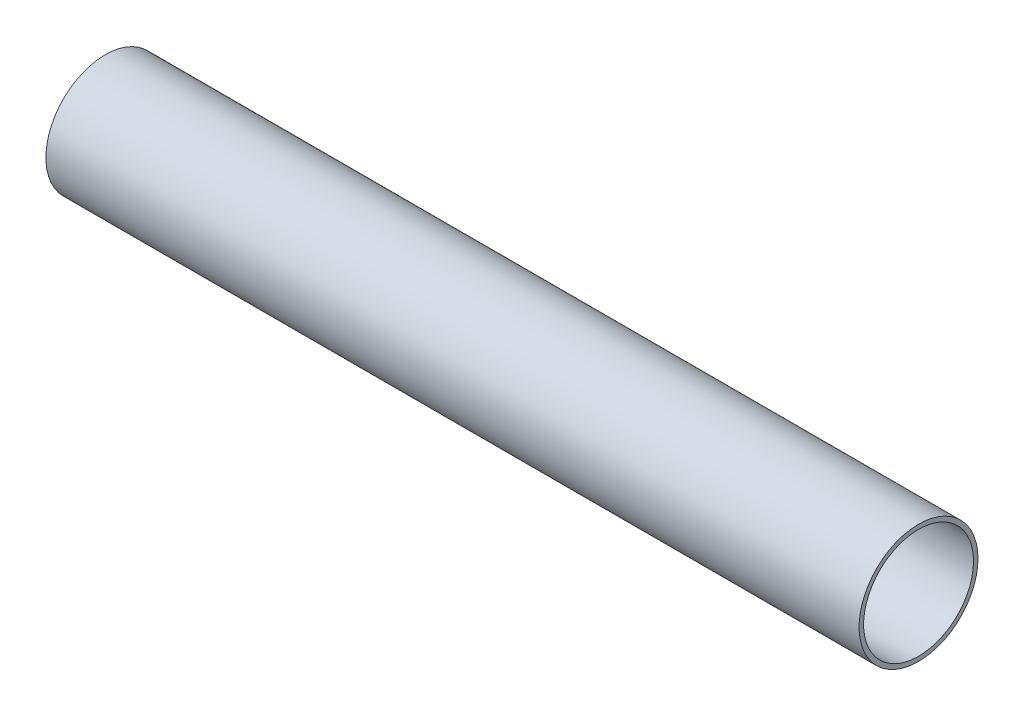
SolidWorks part; units mm, degrees
material "Silicon Rubber"
ref_plane "Front Plane" through (0, 0, 0) normal (0, 0, 1) x (1, 0, 0)
ref_plane "Top Plane" through (0, 0, 0) normal (0, 1, 0) x (1, 0, 0)
ref_plane "Right Plane" through (0, 0, 0) normal (1, 0, 0) x (0, 0, -1)
sketch "Sketch1" plane through (0, 0, 0) normal (1, 0, 0) x (0, 0, -1)
  circle A0 centre (0, 0) radius 15.875
  circle A1 centre (0, 0) radius 17.1714
  dimension "D1" = 31.75
  dimension "D2" = 34.3429
extrude "Boss-Extrude1" add sketch "Sketch1" along normal mid plane 234.9183
equation "\"D2@Sketch1\"=sqr((1.25)^2+(1.125)^2-1)"
